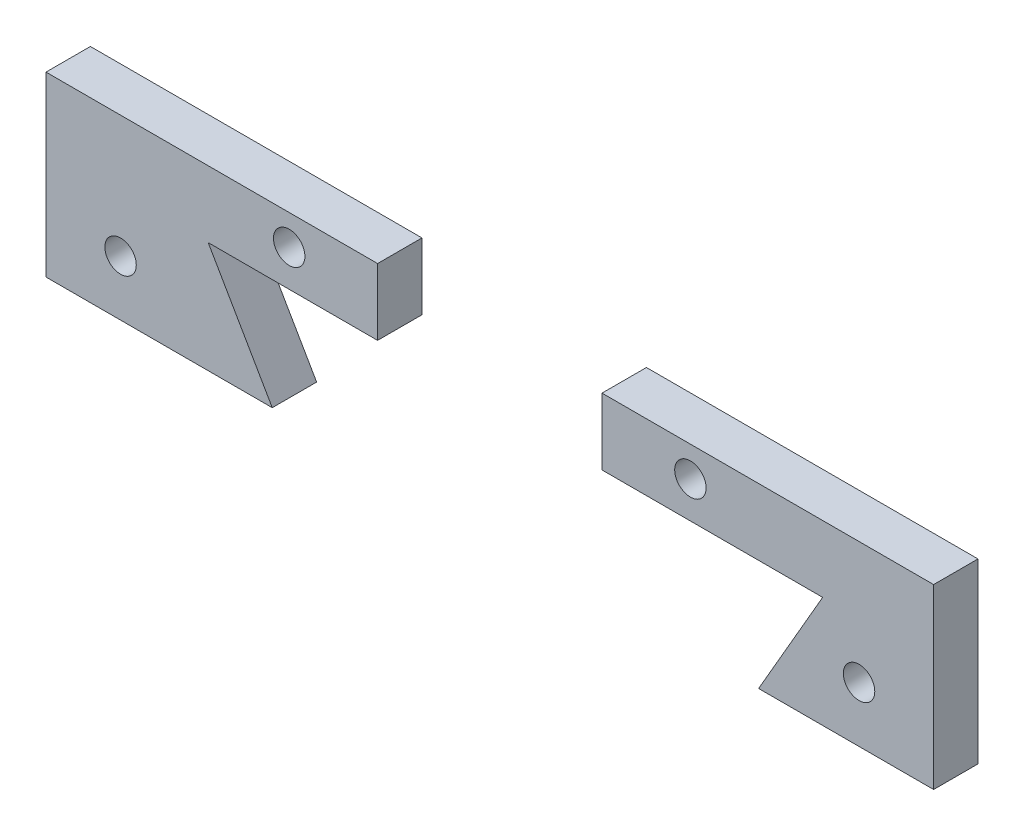
SolidWorks part; units mm, degrees
material "SAE F5 Wool Felt"
ref_plane "Front Plane" through (0, 0, 0) normal (0, 0, 1) x (1, 0, 0)
ref_plane "Top Plane" through (0, 0, 0) normal (0, 1, 0) x (1, 0, 0)
ref_plane "Right Plane" through (0, 0, 0) normal (1, 0, 0) x (0, 0, -1)
sketch "Sketch4" plane through (0, 0, 0) normal (0, 0, 1) x (1, 0, 0)
  point P0 (0, 0)
  line B0 (-63.5, -15.875) -> (63.5, -15.875)
  line B1 (63.5, 0) -> (38.4596, 0)
  line B2 (38.4596, 0) -> (47.625, 15.875)
  line B3 (47.625, 15.875) -> (16.0563, 15.875)
  line B4 (-40.2927, 15.875) -> (-31.1272, 0)
  line B5 (-31.1272, 0) -> (-63.5, 0)
  line B6 (-38.4596, 0) -> (-47.625, 15.875)
  line B7 (-47.625, 15.875) -> (-40.2927, 15.875)
  line B8 (-16.0563, 15.875) -> (-16.0563, -3.175)
  line B9 (-16.0563, 15.875) -> (-40.2927, 15.875)
  line B10 (-63.5, 0) -> (-63.5, 31.75)
  line B11 (-63.5, 31.75) -> (63.5, 31.75)
  line B12 (-16.0563, 15.875) -> (16.0563, 15.875)
  line B13 (0, 31.75) -> (0, -15.875) construction
  line B14 (-38.4596, 0) -> (38.4596, 0) construction
  line B15 (-28.702, 21.082) -> (28.702, 21.082) construction
  line B16 (-25.4, -8.001) -> (25.4, -8.001) construction
  line B17 (-52.832, 7.9375) -> (52.832, 7.9375) construction
  circle B18 centre (0, 6.35) radius 18.669 construction
sketch_block_instance "dovetail pair-1"
sketch_block "dovetail pair" parameters "D8"=37.338, "D1"=60, "D2"=127, "D3"=6.35, "D4"=15.875, "D5"=31.75, "D6"=95.25, "D7"=19.05, "D9"=60, "D10"=31.75, "D11"=50.8, "D12"=23.876, "D13"=7.874, "D14"=10.668, "D15"=34.798, "D16"=21.082, "D17"=7.9375
sketch "Sketch1" plane through (0, 0, 0) normal (0, 0, 1) x (1, 0, 0)
  line L0 (-31.1272, 0) -> (-63.5, 0) construction
  line L1 (-40.2927, 15.875) -> (-31.1272, 0) construction
  line L2 (38.4596, 0) -> (47.625, 15.875) construction
  line L3 (63.5, 0) -> (38.4596, 0) construction
  line L4 (-16.0563, 15.875) -> (-40.2927, 15.875) construction
  line L5 (47.625, 15.875) -> (16.0563, 15.875) construction
  line L6 (-31.1272, 0) -> (-63.5, 0)
  line L7 (-40.2927, 15.875) -> (-31.1272, 0)
  line L8 (38.4596, 0) -> (47.625, 15.875)
  line L9 (63.5, 0) -> (38.4596, 0)
  line L10 (-16.0563, 15.875) -> (-40.2927, 15.875)
  line L11 (47.625, 15.875) -> (16.0563, 15.875)
  line L12 (-63.5, 0) -> (-63.5, 25.4)
  line L13 (-63.5, 25.4) -> (-16.0563, 25.4)
  line L14 (-16.0563, 25.4) -> (-16.0563, 15.875)
  line L15 (16.0563, 15.875) -> (16.0563, 25.4)
  line L16 (16.0563, 25.4) -> (63.5, 25.4)
  line L17 (63.5, 25.4) -> (63.5, 0)
  dimension "D1" = 25.4
extrude "Boss-Extrude1" add sketch "Sketch1" along normal blind 6.35
hole_wizard "#8 Clearance Hole1" positions "Sketch2" profile "Sketch3" hole size "#8" standard "ANSI Inch" end condition through all
sketch "Sketch2" plane through (0, -15.875, 6.35) normal (0, 0, 1) x (1, 0, 0)
  point P32 (-52.832, 23.8125)
  point P34 (-28.702, 36.957)
  point P36 (28.702, 36.957)
  point P38 (52.832, 23.8125)
sketch "Sketch3" plane through (-52.832, 7.9375, 6.35) normal (1, 0, 0) x (0, -1, 0)
  line L0 (0, 0) -> (0, 6.35)
  line L1 (0, 6.35) -> (2.2479, 6.35)
  line L2 (2.2479, 6.35) -> (2.2479, 0)
  line L3 (2.2479, 0) -> (0, 0)
  line L4 (0, -6.35) -> (0, 107.95) construction
  dimension "Thru Hole Dia." = 4.4958
  dimension "Thru Hole Depth" = 6.35
equation "\"dovetail-angle\" = 60"
equation "\"dovetail-stock-width\" = 5"
equation "\"dovetail-stock-height\" = 1.25"
equation "\"dovetail-depth\" = 0.5 * \"dovetail-stock-height\""
equation "\"dovetail-throat-width\" = \"dovetail-stock-width\" - (2 * \"dovetail-depth\")"
equation "\"delta-x\" = 6"
equation "\"delta-y\" = 3"
equation "\"gib-thickness\" = 0.25"
equation "\"x-slide-length\" = \"dovetail-stock-width\" + \"delta-x\""
equation "\"y-slide-length\" = \"dovetail-stock-width\" + \"delta-y\""
equation "\"dog-point-diam\" = .149"
equation "\"dog-point-length\" = .067"
equation "\"dovetail-double-height\" = 2 * \"dovetail-depth\" + 0.5"
equation "\"acme-major-diam\" = .5"
equation "\"acme-pitch-diam\" = 0.45"
equation "\"acme-minor-diam\" = 0.4"
equation "\"acme-nut-od\" = 1.47"
equation "\"acme-nut-length\" = 1"
equation "\"acme-nut-trim-height\" = .75"
equation "\"screw-bearing-od\" = 0.5"
equation "\"screw-bearing-length\" = .375"
equation "\"screw-bearing-id\" = .3125"
equation "\"end-plate-thickness\" = \"screw-bearing-length\""
equation "\"screw-add-length\" = 2 * \"end-plate-thickness\" + 1 + 0.5"
equation "\"x-screw-length\" = \"x-slide-length\" + \"screw-add-length\""
equation "\"y-screw-length\" = \"y-slide-length\" + \"screw-add-length\""
equation "\"acme-nut-mount-hole-space-horz\" = 0.95"
equation "\"acme-nut-mount-hole-space-vert\" = 0.5 * \"acme-nut-length\""
equation "\"vise-hole-center-dist\" = 6.75"
equation "\"wiper_plate_clearance\" = .03"
equation "\"D2@dovetail pair\"=\"dovetail-stock-width\""
equation "\"D1@dovetail pair\"=\"dovetail-angle\""
equation "\"D3@dovetail pair\"=\"gib-thickness\""
equation "\"D4@dovetail pair\"=\"dovetail-depth\""
equation "\"D5@dovetail pair\"=\"dovetail-stock-height\""
equation "\"D6@dovetail pair\"=\"dovetail-throat-width\""
equation "\"D10@dovetail pair\"=\"dovetail-stock-height\""
equation "\"D7@dovetail pair\"=\"acme-nut-trim-height\""
equation "\"D8@dovetail pair\"=\"acme-nut-od\""
equation "\"D9@dovetail pair\"=\"dovetail-angle\""
equation "\"D17@dovetail pair\"=\"dovetail-depth\"/2"
